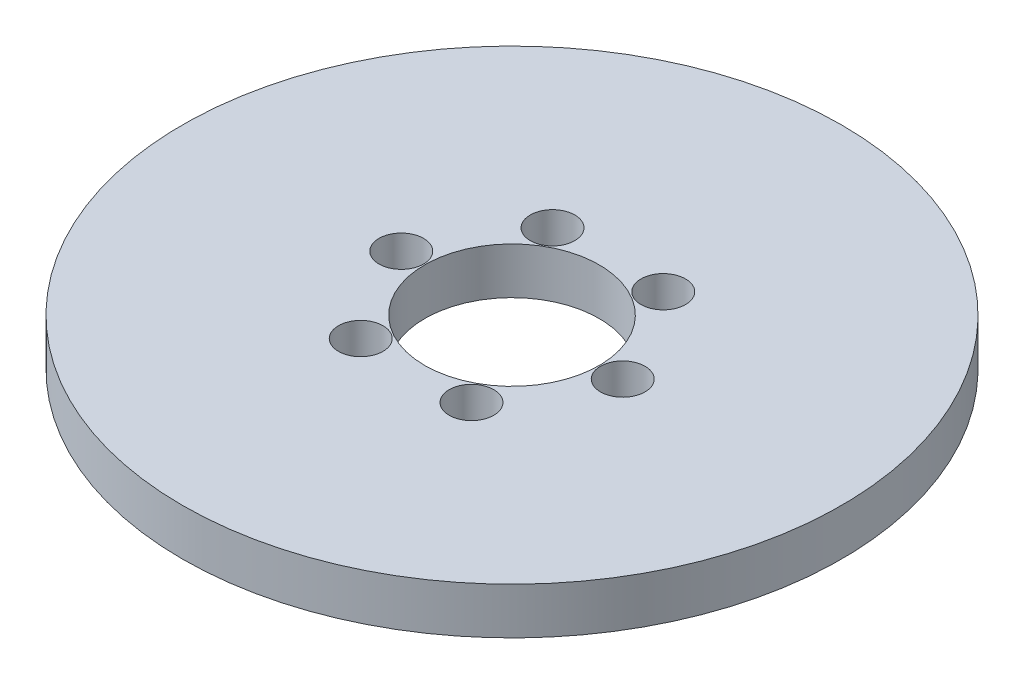
SolidWorks part; units mm, degrees
ref_plane "Front Plane" through (0, 0, 0) normal (0, 0, 1) x (1, 0, 0)
ref_plane "Top Plane" through (0, 0, 0) normal (0, 1, 0) x (1, 0, 0)
ref_plane "Right Plane" through (0, 0, 0) normal (1, 0, 0) x (0, 0, -1)
sketch "Sketch1" plane through (0, 0, 0) normal (0, 1, 0) x (1, 0, 0)
  circle A0 centre (0, 0) radius 85
  dimension "FLANGE_OD" = 170
extrude "Boss-Extrude1" add sketch "Sketch1" along normal blind 12
sketch "Sketch2" plane through (0, 0, 0) normal (0, 1, 0) x (1, 0, 0)
  circle A0 centre (0, 0) radius 22.5
  dimension "BORE_D" = 45
extrude "Cut-Extrude1" cut sketch "Sketch2" along normal through all
sketch "Sketch3" plane through (0, 12, 0) normal (0, 1, 0) x (1, 0, 0)
  circle A0 centre (0, 0) radius 28.5606 construction
  circle A1 centre (-28.5606, 0) radius 5.7445
  dimension "BOLT_D" = 11.4889
  dimension "BOLT_PCD" = 57.1213
extrude "Cut-Extrude2" cut sketch "Sketch3" against normal blind 8.6407
pattern_circular "CirPattern1" count 6 over 360 about axis through (0, 0, 0) along (0, 1, 0) of "Cut-Extrude2"
